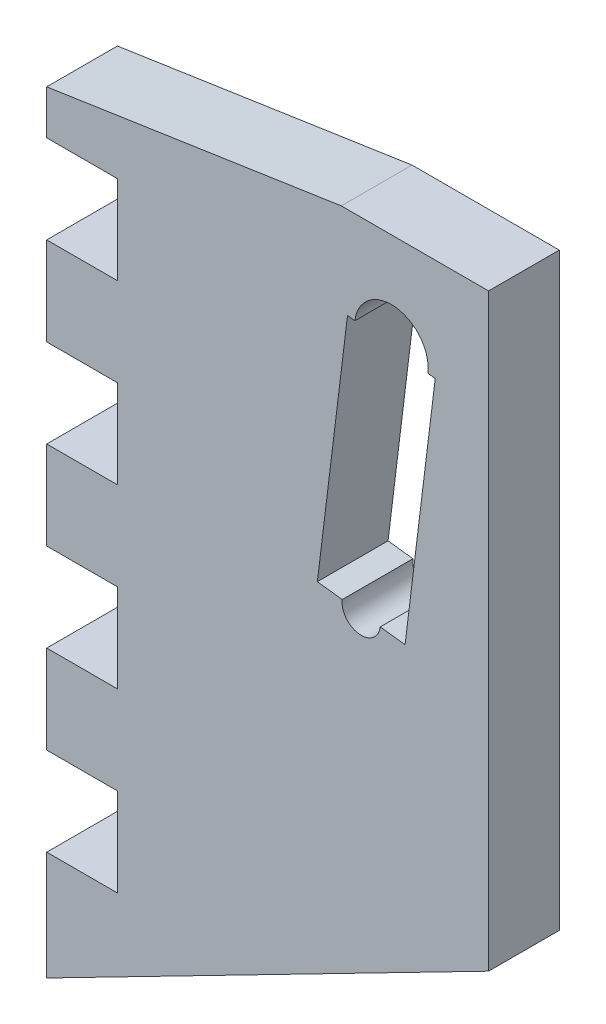
SolidWorks part; units mm, degrees
material "Thornel VCB-20 Carbon Cloth"
ref_plane "Front Plane" through (0, 0, 0) normal (0, 0, 1) x (1, 0, 0)
ref_plane "Top Plane" through (0, 0, 0) normal (0, 1, 0) x (1, 0, 0)
ref_plane "Right Plane" through (0, 0, 0) normal (1, 0, 0) x (0, 0, -1)
sketch "Sketch1" plane through (0, 0, 0) normal (0, 0, 1) x (1, 0, 0)
  line L0 (0, 0) -> (-38.1, 0)
  line L1 (0, 0) -> (0, -50.8)
  line L2 (-38.1, 0) -> (-38.1, -7.62)
  line L3 (-38.1, -7.62) -> (-32.004, -7.62)
  line L4 (-32.004, -7.62) -> (-32.004, -15.24)
  line L5 (-32.004, -15.24) -> (-38.1, -15.24)
  line L6 (-38.1, -45.72) -> (-38.1, -70.358)
  line L7 (-38.1, -15.24) -> (-38.1, -22.86)
  line L8 (-38.1, -22.86) -> (-32.004, -22.86)
  line L9 (-32.004, -22.86) -> (-32.004, -30.48)
  line L10 (-32.004, -30.48) -> (-38.1, -30.48)
  line L11 (-38.1, -30.48) -> (-38.1, -38.1)
  line L12 (-38.1, -38.1) -> (-32.004, -38.1)
  line L13 (-32.004, -38.1) -> (-32.004, -45.72)
  line L14 (-32.004, -45.72) -> (-38.1, -45.72)
  line L15 (-38.1, -70.358) -> (0, -50.8)
  circle A0 centre (-8.382, -8.382) radius 3.175
  dimension "D9" = 6.35
  dimension "D1" = 38.1
  dimension "D2" = 50.8
  dimension "D3" = 7.62
  dimension "D4" = 7.62
  dimension "D6" = 6.096
  dimension "D8" = 70.358
  dimension "D12" = 8.382
  dimension "D13" = 8.382
  dimension "D7" = 3
extrude "Boss-Extrude1" add sketch "Sketch1" along normal blind 6.096 contours L6 L15 L1 L0 L2 L3 L4 L5 L7 L8 L9 L10 L11 L12 L13 L14 A0 region at (-19.2717, -31.1343, 0)
sketch "Sketch2" plane through (0, 0, 0) normal (0, 0, -1) x (-1, 0, 0)
  line L5 (38.1, 0) -> (12.7, 0)
  line L6 (0, 0) -> (38.1, 0) construction
  line L7 (12.7, 0) -> (38.1, -3.81)
  line L8 (38.1, 0) -> (38.1, -7.62) construction
  line L9 (38.1, -3.81) -> (38.1, 0)
  dimension "D1" = 25.4
  dimension "D2" = 3.81
extrude "Cut-Extrude1" cut sketch "Sketch2" against normal blind 8.636
sketch "Sketch4" plane through (0, 0, 6.096) normal (0, 0, 1) x (1, 0, 0)
  line L0 (-38.1, -45.72) -> (-38.1, -53.34)
  line L1 (-38.1, -45.72) -> (-38.1, -70.358) construction
  line L2 (-38.1, -53.34) -> (-32.004, -53.34)
  line L3 (-32.004, -53.34) -> (-32.004, -60.96)
  line L4 (-32.004, -60.96) -> (-38.1, -60.96)
  line L5 (-38.1, -60.96) -> (-38.1, -53.34)
  line M18 (-38.1, -45.72) -> (-38.1, -70.358)
  dimension "D1" = 7.62
  dimension "D2" = 6.096
  dimension "D3" = 6.096
  dimension "D4" = 7.62
extrude "Cut-Extrude2" cut sketch "Sketch4" against normal through all contours L4 L3 L2 M18 region at (-35.052, -57.15, 6.096)
sketch "Sketch5" plane through (0, 0, 0) normal (0, 0, -1) x (-1, 0, 0)
  line L0 (8.382, -8.382) -> (10.9822, -29.559) construction
  line L1 (8.382, -8.382) -> (8.382, -39.2411) construction
  circle A0 centre (8.382, -8.382) radius 3.175 construction
  circle A1 centre (10.9822, -29.559) radius 1.651
  dimension "D1" = 21.336
  dimension "D2" = 7
extrude "Cut-Extrude4" cut sketch "Sketch5" against normal up to surface (6.096 mm away) up to face at (-5.207, -8.382, 6.096)
sketch "Sketch6" plane through (0, 0, 6.096) normal (0, 0, 1) x (1, 0, 0)
  line L0 (-5.2307, -8.7689) -> (-4.6004, -8.8463)
  line L1 (-11.5333, -7.9951) -> (-12.1636, -7.9177)
  line L6 (-14.7638, -29.0946) -> (-12.6209, -29.3578)
  line L7 (-4.6004, -8.8463) -> (-7.2006, -30.0233)
  line L8 (-12.1636, -7.9177) -> (-14.7638, -29.0946)
  line L10 (-9.3435, -29.7602) -> (-7.2006, -30.0233)
  line L11 (-12.6209, -29.3578) -> (-9.3435, -29.7602)
  line L12 (-11.5333, -7.9951) -> (-5.2307, -8.7689)
  dimension "D5" = 21.336
  dimension "D2" = 0.635
  dimension "D3" = 0.635
extrude "Cut-Extrude5" cut sketch "Sketch6" against normal up to surface (6.096 mm away) up to face at (-12.6332, -29.559, 0)
